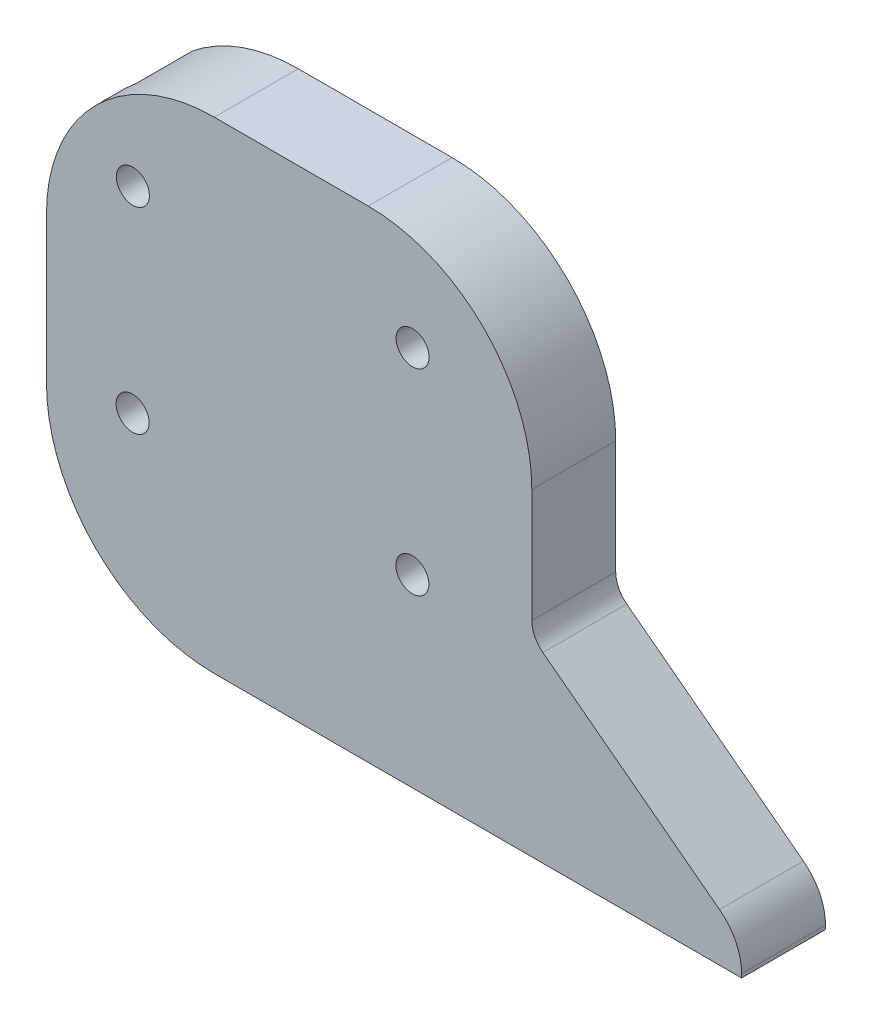
SolidWorks part; units mm, degrees
ref_plane "Front Plane" through (0, 0, 0) normal (0, 0, 1) x (1, 0, 0)
ref_plane "Top Plane" through (0, 0, 0) normal (0, 1, 0) x (1, 0, 0)
ref_plane "Right Plane" through (0, 0, 0) normal (1, 0, 0) x (0, 0, -1)
sketch "Sketch1" plane through (0, 0, 0) normal (0, 0, 1) x (1, 0, 0)
  line L5 (-37.5542, 16.3443) -> (-37.5542, -14.7707)
  line L6 (-8.3442, 16.3443) -> (-37.5542, 16.3443)
  line L7 (3.0858, -14.7707) -> (3.0858, 4.9143)
  line L14 (-8.3442, 19.7733) -> (-37.5542, 19.7733)
  line L16 (-37.5542, -18.1997) -> (6.5148, -18.1997)
  line L18 (-37.5542, -14.7707) -> (3.0858, -14.7707)
  line L19 (6.5148, -18.1997) -> (6.5148, 4.9143)
  line L20 (-40.9832, 19.7733) -> (-40.9832, -18.1997) construction
  line L21 (-37.5542, 16.3443) -> (-37.5542, 19.7733)
  line L23 (-37.5542, -14.7707) -> (-37.5542, -18.1997)
  line L24 (-8.3442, 19.7733) -> (-40.9832, 19.7733) construction
  line L25 (-40.9832, -18.1997) -> (6.5148, -18.1997) construction
  line L26 (-37.5542, -18.1997) -> (6.5148, -18.1997)
  line L27 (-37.5542, -18.1997) -> (-37.5542, -21.4382)
  line L28 (6.5148, -18.1997) -> (6.5148, -21.4382)
  line L29 (-37.5542, -21.4382) -> (6.5148, -21.4382)
  line L30 (6.5148, -6.6427) -> (25.5648, -21.1207)
  line L32 (32.3202, -21.1207) -> (-19.7742, -21.1207) construction
  line L33 (25.5648, -21.1207) -> (6.5148, -21.4382)
  circle A5 centre (-29.7105, 10.6454) radius 1.5
  circle A6 centre (-4.3105, 10.6454) radius 1.5
  circle A7 centre (-29.7329, -7.2154) radius 1.5
  circle A8 centre (-4.3329, -7.2154) radius 1.5
  arc A9 (3.0858, 4.9143) -> (-8.3442, 16.3443) centre (-8.3442, 4.9143) ccw
  arc A10 (6.5148, 4.9143) -> (-8.3442, 19.7733) centre (-8.3442, 4.9143) ccw
  dimension "D1" = 3.429
  dimension "D2" = 3.2385
  dimension "D3" = 19.05
  dimension "D6" = 29.21
extrude "Boss-Extrude1" add sketch "Sketch1" against normal blind 7.62 contours L19 A10 L14 L21 L6 A9 L7 L18 L23 L16 | L33 L30 L19 L28 | L27 L29 L28 L16 region at (-36.9725, 18.0588, 0) region at (-15.5197, -19.8189, 0) region at (12.8648, -16.4005, 0)
extrude "Boss-Extrude2" add sketch "Sketch1<3>" against normal blind 2.54 contours L7 A9 L6 L5 A5 A6 A7 A8 region at (-17.6515, 0.4633, 0)
sketch "Sketch1<3>" plane through (0, 0, 0) normal (0, 0, 1) x (1, 0, 0) same geometry as "Sketch1"
sketch "Sketch2" plane through (0, -21.4382, 0) normal (0, -1, 0) x (1, 0, 0)
  line L4 (25.5648, 0) -> (6.5148, 0)
  line L5 (6.5148, 0) -> (6.5148, -7.62)
  line L6 (6.5148, -7.62) -> (25.5648, -7.62)
  line L7 (25.5648, -7.62) -> (25.5648, 0)
  line L8 (25.5648, 0) -> (6.5148, 0)
  line L9 (6.5148, 0) -> (6.5148, -7.62)
  line L10 (6.5148, -7.62) -> (25.5648, -7.62)
  line L12 (6.5148, 0) -> (-37.5542, 0)
  line L13 (-37.5542, 0) -> (-37.5542, -7.62)
  line L14 (-37.5542, -7.62) -> (6.5148, -7.62)
  line L15 (6.5148, -7.62) -> (6.5148, 0)
  line L16 (6.5148, 0) -> (-37.5542, 0)
  line L18 (-37.5542, -7.62) -> (6.5148, -7.62)
  line L19 (6.5148, -7.62) -> (6.5148, 0)
  line L22 (25.5648, -7.62) -> (25.5648, 0)
  line L23 (-37.5542, 0) -> (-37.5542, -7.62)
  line M9 (6.5148, 0) -> (-37.5542, 0)
  line M10 (-37.5542, 0) -> (-37.5542, -7.62)
  line M11 (-37.5542, -7.62) -> (6.5148, -7.62)
  line M12 (6.5148, -7.62) -> (6.5148, 0)
  dimension "D1" = 0
  dimension "D2" = 0
extrude "Boss-Extrude3" add sketch "Sketch2" along normal blind 2.54 and the other way up to surface contours L10 L22 L8 M12 | M12 M9 M10 M11 region at (16.0398, -21.4382, -3.81) region at (-15.5197, -21.4382, -3.81) other way up to face at (16.0398, -21.2794, -3.81)
fillet "Fillet1" radius 15.24 2 edges at (-37.5542, 19.7733, -3.81) (-37.5542, -23.9782, -3.81)
fillet "Fillet2" radius 5.08 1 edges at (25.5648, -21.1207, -3.81)
fillet "Fillet3" radius 2.54 1 edges at (6.5148, -6.6427, -3.81)
